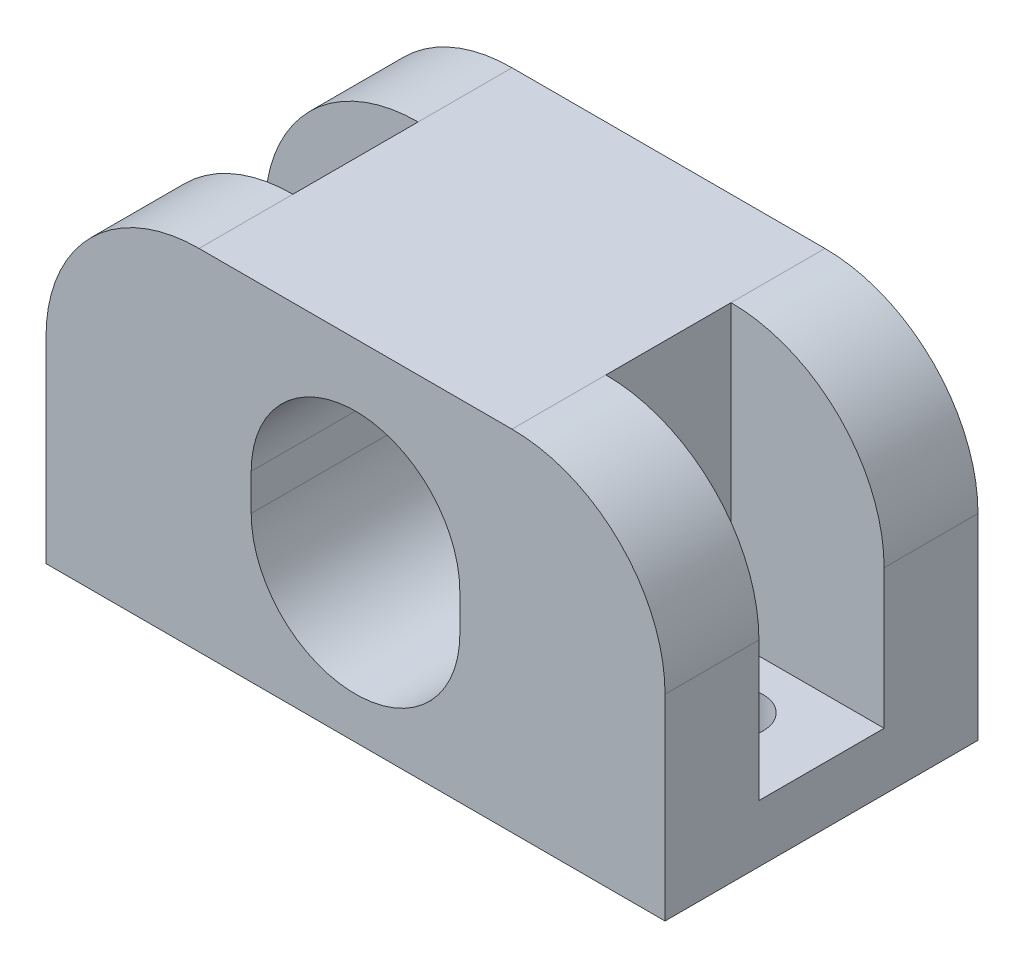
SolidWorks part; units mm, degrees
ref_plane "Front Plane" through (0, 0, 0) normal (0, 0, 1) x (1, 0, 0)
ref_plane "Top Plane" through (0, 0, 0) normal (0, 1, 0) x (1, 0, 0)
ref_plane "Right Plane" through (0, 0, 0) normal (1, 0, 0) x (0, 0, -1)
sketch "Sketch1" plane through (0, 0, 0) normal (0, 0, 1) x (1, 0, 0)
  line L0 (0, 0) -> (0, 11.75) construction
  line L3 (0, -2) -> (-14.835, -2)
  line L4 (-14.835, -2) -> (-14.835, 7.415)
  line L6 (-7.5, 14.75) -> (7.5, 14.75)
  line L8 (14.835, -2) -> (14.835, 7.415)
  line L9 (0, -2) -> (14.835, -2)
  line L13 (-5, 6.75) -> (-5, 5)
  line L14 (5, 6.75) -> (5, 5)
  line L17 (0, 5.875) -> (12.4697, 5.875) construction
  line L18 (0, -2) -> (0, 0) construction
  arc A0 (-5, 6.75) -> (5, 6.75) centre (0, 6.75) cw
  arc A1 (-5, 5) -> (5, 5) centre (0, 5) ccw
  arc A2 (-7.5, 14.75) -> (-14.835, 7.415) centre (-7.5, 7.415) ccw
  arc A3 (7.5, 14.75) -> (14.835, 7.415) centre (7.5, 7.415) cw
  point P4 (0, 14.75)
  point P6 (0, 0)
  point P16 (0, 0)
  point P23 (-14.835, 7.415)
  point P24 (-7.5, 14.75)
  point P25 (0, 0)
  dimension "D1" = 2
  dimension "D2" = 7.875
  dimension "D3" = 29.67
  dimension "D4" = 15
  dimension "D6" = 6.75
  dimension "D7" = 10
  dimension "D8" = 8
extrude "Boss-Extrude1" add sketch "Sketch1" against normal blind 15
sketch "Sketch2" plane through (0, 14.75, 0) normal (0, 1, 0) x (1, 0, 0)
  line L12 (-14.835, 7.5) -> (14.835, 7.5) construction
  line L13 (14.835, 15) -> (14.835, 0) construction
  line L14 (-14.835, 15) -> (-14.835, 0) construction
  line L26 (-7.5, 15) -> (-7.5, 0) construction
  line L27 (-7.5, 15) -> (-14.835, 15) construction
  line L30 (0, 15) -> (0, 0) construction
  line L31 (7.5, 15) -> (-7.5, 15) construction
  line L32 (7.5, 0) -> (-7.5, 0) construction
  line L40 (-10.5425, 15) -> (-10.5425, 0) construction
  line L43 (-14.835, 10.5) -> (-7.5, 10.5)
  line L46 (-14.835, 4.5) -> (-7.5, 4.5)
  line L47 (-7.5, 10.5) -> (-7.5, 4.5)
  line L48 (-14.835, 10.5) -> (-14.835, 4.5)
  circle A10 centre (-10.5425, 7.5) radius 1.5
  point P5 (-10.5425, 15)
  point P7 (-21.7538, 7.5)
  point P8 (-14.835, 7.5)
  point P17 (0, 0)
  point P18 (0, 0)
  point P20 (-10.5425, 7.5)
  point P21 (0, 0)
  point P22 (-7.5, 10.5)
  point P27 (0, 0)
  point P34 (0, 0)
  point P35 (0, 0)
  dimension "D1" = 3
  dimension "D2" = 3
  dimension "D4" = 4.2925
extrude "Cut-Extrude1" cut sketch "Sketch2" against normal blind 14 contours L48 L46 L47 L43
extrude "Cut-Extrude2" cut sketch "Sketch2<3>" against normal through all contours A10 region at (-10.5425, 14.75, -7.5)
sketch "Sketch2<3>" plane through (0, 14.75, 0) normal (0, 1, 0) x (1, 0, 0) same geometry as "Sketch2"
mirror "Mirror1" about plane through (0, 0, 0) normal (1, 0, 0) of "Cut-Extrude2", "Cut-Extrude1"
